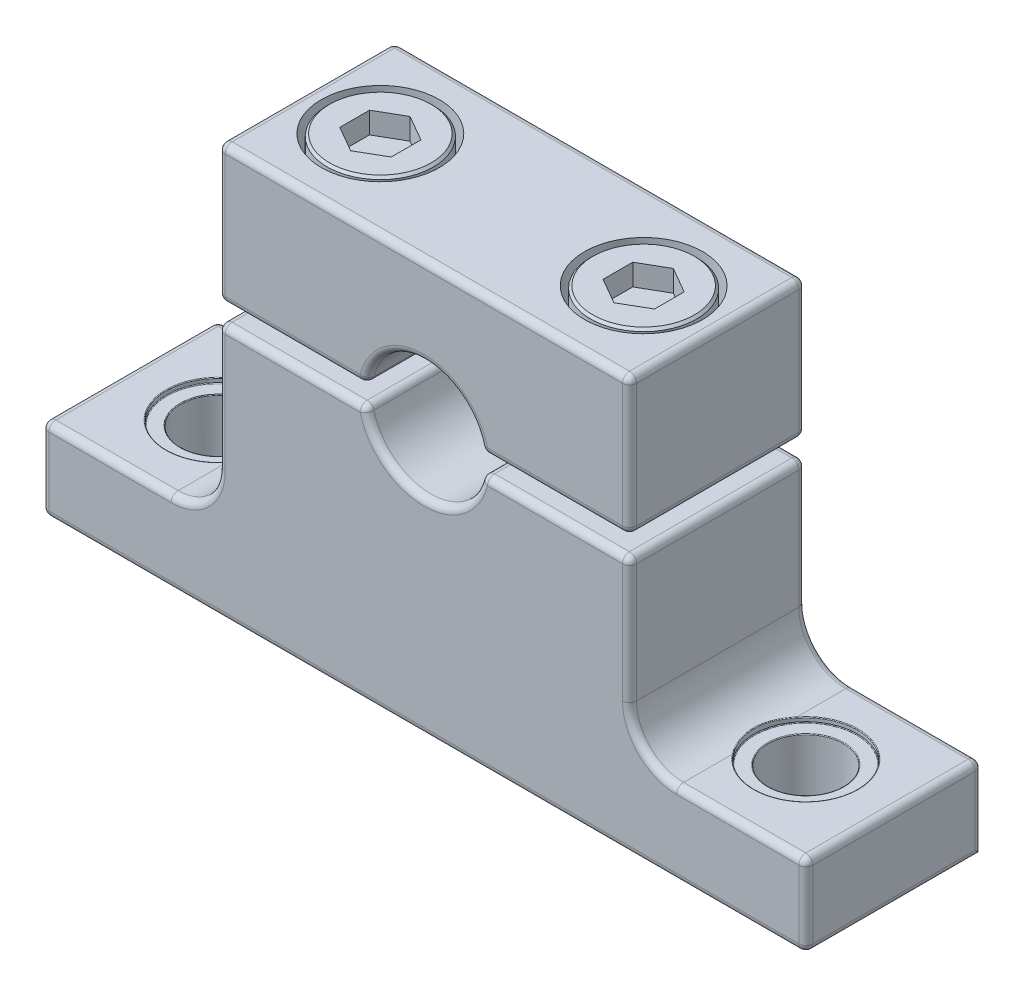
SolidWorks part; units mm, degrees
ref_plane "Front" through (0, 0, 0) normal (0, 0, 1) x (1, 0, 0)
ref_plane "Top" through (0, 0, 0) normal (0, 1, 0) x (1, 0, 0)
ref_plane "Right" through (0, 0, 0) normal (1, 0, 0) x (0, 0, -1)
sketch "Sketch1" plane through (0, 0, 0) normal (0, 0, 1) x (1, 0, 0)
  line L0 (0, 22.225) -> (0, 0) construction
  line L1 (-20.6375, 0) -> (20.6375, 0) construction
  line L2 (0, 0) -> (0, 14.2875) construction
  line L3 (-15.875, 0) -> (15.875, 0) construction
  line L4 (13.843, 0) -> (17.907, 0) construction
  line L5 (17.907, 0) -> (17.907, 1.27) construction
  line L6 (13.843, 0) -> (13.843, 1.27) construction
  line L7 (-13.843, 0) -> (-13.843, 1.27) construction
  line L8 (-17.907, 0) -> (-17.907, 1.27) construction
  line L9 (-13.843, 0) -> (-17.907, 0) construction
  line L10 (-11.1125, 14.2875) -> (11.1125, 14.2875) construction
  line L11 (-11.1125, 13.7795) -> (11.1125, 13.7795) construction
  line L12 (-11.1125, 14.7955) -> (11.1125, 14.7955) construction
  line L13 (13.462, 0) -> (13.462, 1.27) construction
  line L14 (18.288, 0) -> (18.288, 1.27) construction
  line L15 (-13.462, 0) -> (-13.462, 1.27) construction
  line L16 (-18.288, 0) -> (-18.288, 1.27) construction
  line L17 (-11.0713, 13.7795) -> (11.0713, 13.7795) construction
  line L18 (-11.0713, 14.7955) -> (11.0713, 14.7955) construction
  line L19 (-11.0713, 14.2875) -> (11.0713, 14.2875) construction
  line L20 (-20.6375, 0) -> (-20.6375, 4.445) construction
  line L21 (-20.6375, 4.445) -> (-11.1125, 4.445) construction
  line L22 (-11.1125, 13.7795) -> (-11.1125, 4.445) construction
  line L23 (-11.1125, 14.7955) -> (-11.1125, 22.225) construction
  line L24 (-11.1125, 22.225) -> (11.1125, 22.225) construction
  line L25 (20.6375, 0) -> (20.6375, 4.445) construction
  line L26 (20.6375, 4.445) -> (11.1125, 4.445) construction
  line L27 (11.1125, 13.7795) -> (11.1125, 4.445) construction
  line L28 (11.1125, 14.7955) -> (11.1125, 22.225) construction
  line L29 (0, 22.225) -> (0, 18.7198) construction
  line L30 (0.3175, 18.7198) -> (-0.3175, 18.7198) construction
  line L31 (11.1125, 4.445) -> (11.1125, 0) construction
  line L32 (-15.875, 0) -> (-15.875, 4.445) construction
  line L33 (0, 17.4625) -> (11.1125, 17.4625) construction
  line L34 (0, 11.1125) -> (11.1125, 11.1125) construction
  circle A0 centre (0, 14.2875) radius 3.175 construction
  arc A1 (-13.6525, 4.445) -> (-11.1125, 6.985) centre (-13.6525, 6.985) ccw construction
  arc A2 (13.6525, 4.445) -> (11.1125, 6.985) centre (13.6525, 6.985) cw construction
  point P5 (0, 0)
  point P9 (0, 14.2875)
  point P11 (0, 0)
  point P12 (15.875, 0)
  point P13 (-15.875, 0)
  point P16 (15.875, 0)
  point P37 (0, 13.7795)
  point P40 (0, 14.7955)
  point P60 (0, 18.7198)
  point P64 (15.875, 4.445)
  dimension "D1" = 1.27
  dimension "D8" = 4.445
  dimension "D12" = 0.635
  dimension "Radius" = 2.54
  dimension "D9" = 4.7625
  dimension "D3" = 0.508
  dimension "D4" = 0.381
  dimension "D5" = 0.381
  dimension "D6" = 0.381
  dimension "D7" = 0.381
sketch "Sketch3" plane through (0, 0, 0) normal (0, 0, 1) x (1, 0, 0)
  line L0 (-11.1125, 22.225) -> (11.1125, 22.225) construction
  line L1 (11.1125, 14.7955) -> (11.1125, 22.225) construction
  line L2 (-11.1125, 14.7955) -> (11.1125, 14.7955) construction
  line L3 (-11.1125, 14.7955) -> (-11.1125, 22.225) construction
  line L4 (-11.1125, 13.7795) -> (-11.1125, 4.445) construction
  line L5 (-20.6375, 4.445) -> (-11.1125, 4.445) construction
  line L6 (-20.6375, 0) -> (-20.6375, 4.445) construction
  line L7 (-20.6375, 0) -> (20.6375, 0) construction
  line L8 (20.6375, 0) -> (20.6375, 4.445) construction
  line L9 (20.6375, 4.445) -> (11.1125, 4.445) construction
  line L10 (11.1125, 13.7795) -> (11.1125, 4.445) construction
  line L11 (-11.1125, 13.7795) -> (11.1125, 13.7795) construction
  line L12 (-11.1125, 22.225) -> (11.1125, 22.225)
  line L13 (11.1125, 14.7955) -> (11.1125, 22.225)
  line L14 (-11.1125, 14.7955) -> (-3.1341, 14.7955)
  line L15 (-11.1125, 14.7955) -> (-11.1125, 22.225)
  line L16 (-11.1125, 13.7795) -> (-11.1125, 6.985)
  line L17 (-20.6375, 4.445) -> (-13.6525, 4.445)
  line L18 (-20.6375, 0) -> (-20.6375, 4.445)
  line L19 (-20.6375, 0) -> (20.6375, 0)
  line L20 (20.6375, 0) -> (20.6375, 4.445)
  line L21 (20.6375, 4.445) -> (13.6525, 4.445)
  line L22 (11.1125, 13.7795) -> (11.1125, 6.985)
  line L23 (-11.1125, 13.7795) -> (-3.1341, 13.7795)
  line L24 (3.1341, 14.7955) -> (11.1125, 14.7955)
  line L25 (3.1341, 13.7795) -> (11.1125, 13.7795)
  arc A0 (-13.6525, 4.445) -> (-11.1125, 6.985) centre (-13.6525, 6.985) ccw construction
  arc A1 (11.1125, 6.985) -> (13.6525, 4.445) centre (13.6525, 6.985) ccw construction
  circle A2 centre (0, 14.2875) radius 3.175 construction
  arc A3 (-13.6525, 4.445) -> (-11.1125, 6.985) centre (-13.6525, 6.985) ccw
  arc A4 (11.1125, 6.985) -> (13.6525, 4.445) centre (13.6525, 6.985) ccw
  arc A5 (3.1341, 14.7955) -> (-3.1341, 14.7955) centre (0, 14.2875) ccw
  arc A6 (-3.1341, 13.7795) -> (3.1341, 13.7795) centre (0, 14.2875) ccw
extrude "Boss-Extrude1" add sketch "Sketch3" against normal blind 9.525
sketch "Sketch4" plane through (0, 0, 0) normal (0, -1, 0) x (1, 0, 0)
  line L0 (-20.6375, 0) -> (-20.6375, -9.525) construction
  line L1 (-20.6375, 0) -> (-11.1125, 0) construction
  line L2 (-20.6375, -4.7625) -> (20.6375, -4.7625) construction
  line L3 (20.6375, -9.525) -> (20.6375, 0) construction
  line L4 (-15.875, 0) -> (-15.875, -9.525) construction
  line L5 (15.875, 0) -> (15.875, -9.525) construction
  line L6 (-20.6375, -9.525) -> (20.6375, -9.525) construction
  line L7 (0, 0) -> (0, -9.525) construction
  circle A0 centre (-15.875, -4.7625) radius 2.032
  circle A1 centre (15.875, -4.7625) radius 2.032
  point P7 (-20.6375, -4.7625)
  dimension "D1" = 4.064
extrude "Cut-Extrude1" cut sketch "Sketch4" against normal through all
sketch "Sketch6" plane through (0, 4.445, 0) normal (0, 1, 0) x (1, 0, 0)
  line L0 (0, 0) -> (0, 9.525) construction
  line L1 (-20.6375, 0) -> (20.6375, 0) construction
  line L2 (11.1125, 9.525) -> (-11.1125, 9.525) construction
  circle A1 centre (-15.875, 4.7625) radius 2.032 construction
  circle A2 centre (-15.875, 4.7625) radius 2.032
  circle A4 centre (-15.875, 4.7625) radius 2.413
  circle A5 centre (15.875, 4.7625) radius 2.413
  dimension "D1" = 0.381
sketch "Sketch7" plane through (0, 0, 0) normal (0, 0, 1) x (1, 0, 0)
  line L0 (-20.6375, 4.191) -> (20.6375, 4.191) construction
  line L1 (-11.1125, 13.7795) -> (-11.1125, 0) construction
  line L2 (-20.6375, 0) -> (20.6375, 0) construction
  line L3 (11.1125, 13.7795) -> (11.1125, 0) construction
  line L5 (-20.6375, 0) -> (-20.6375, 4.445) construction
  line L6 (-20.6375, 4.445) -> (-11.1125, 4.445) construction
  line L7 (20.6375, 0) -> (20.6375, 4.445) construction
  line L8 (-15.875, 4.445) -> (-15.875, 4.191) construction
  line L9 (15.875, 4.445) -> (15.875, 4.191) construction
  line L10 (20.6375, 4.445) -> (11.1125, 4.445) construction
  dimension "D1" = 0.254
sketch "Sketch8" plane through (0, 13.7795, 0) normal (0, 1, 0) x (1, 0, 0)
  line L0 (0, 0) -> (0, 9.525) construction
  line L1 (11.1125, 9.525) -> (-11.1125, 9.525) construction
  circle A0 centre (-15.875, 4.7625) radius 2.413 construction
  circle A1 centre (15.875, 4.7625) radius 2.413 construction
  circle A2 centre (-15.875, 4.7625) radius 2.413 construction
  circle A3 centre (15.875, 4.7625) radius 2.413 construction
  circle A4 centre (-15.875, 4.7625) radius 2.794
  circle A5 centre (15.875, 4.7625) radius 2.794
  dimension "CounterBoreID" = 5.588
extrude "Cut-Extrude3" cut sketch "Sketch8" against normal up to vertex (9.5885 mm away) up to point (-15.875, 4.191, 0)
sketch "Sketch10" plane through (0, 22.225, 0) normal (0, 1, 0) x (1, 0, 0)
  line L0 (-11.1125, 9.525) -> (-11.1125, 0) construction
  line L1 (11.1125, 9.525) -> (11.1125, 0) construction
  line L2 (-11.1125, 9.525) -> (-11.1125, 0) construction
  line L3 (11.1125, 9.525) -> (11.1125, 0) construction
  line L4 (-9.9822, 9.525) -> (-9.9822, 0) construction
  line L5 (0, 0) -> (0, 9.525) construction
  line L6 (9.9822, 9.525) -> (9.9822, 0) construction
  circle A0 centre (-7.112, 4.7625) radius 1.7526 construction
  circle A1 centre (7.112, 4.7625) radius 2.0066
  circle A2 centre (-7.112, 4.7625) radius 2.0066
  circle A3 centre (7.112, 4.7625) radius 1.7526 construction
  circle A4 centre (-7.112, 4.7625) radius 2.8702 construction
  circle A5 centre (7.112, 4.7625) radius 2.8702 construction
extrude "Cut-Extrude4" cut sketch "Sketch10" against normal through all
ref_plane "Plane1" through (0, 0, -4.7625) normal (0, 0, 1) x (1, 0, 0)
sketch "Sketch12" plane through (0, 22.225, 0) normal (0, 1, 0) x (1, 0, 0)
  line L0 (0, 9.525) -> (0, 0) construction
  circle A0 centre (-7.112, 4.7625) radius 3.0607 construction
  circle A1 centre (7.112, 4.7625) radius 3.1877
  circle A2 centre (-7.112, 4.7625) radius 3.1877
  circle A3 centre (7.112, 4.7625) radius 3.0607 construction
  dimension "D2" = 6.3754
  dimension "D1" = 0.127
extrude "Cut-Extrude5" cut sketch "Sketch12" against normal blind 3.8862
sketch "Sketch13" plane through (0, 0, 0) normal (0, 1, 0) x (1, 0, 0)
  line L0 (-7.112, 9.525) -> (-7.112, 0) construction
  line L1 (11.1125, 9.525) -> (-11.1125, 9.525) construction
  line L2 (0, 9.525) -> (0, 0) construction
  line L3 (7.112, 9.525) -> (7.112, 0) construction
  circle A0 centre (-7.112, 4.7625) radius 2.0066 construction
  point P2 (-7.112, 4.7625)
  point P9 (-7.112, 9.525)
  point P10 (-7.112, 0)
  point P17 (7.112, 9.525)
  point P18 (7.112, 0)
  dimension "D1" = 4.0132
sketch "Sketch15" plane through (0, 0, -4.7625) normal (0, 0, 1) x (1, 0, 0)
  line L0 (-7.112, 8.89) -> (-7.112, 22.225) construction
  line L1 (-7.112, 22.225) -> (-9.9822, 22.225) construction
  line L2 (-9.9822, 22.225) -> (-9.9822, 18.7198) construction
  line L3 (-9.9822, 18.7198) -> (-8.8646, 18.7198) construction
  line L4 (-8.8646, 18.7198) -> (-8.8646, 8.89) construction
  line L5 (-8.8646, 8.89) -> (-7.112, 8.89) construction
  line L8 (-11.1125, 22.225) -> (11.1125, 22.225) construction
  line L9 (-7.112, 8.89) -> (-7.112, 22.225)
  line L10 (-7.112, 22.225) -> (-9.9822, 22.225)
  line L11 (-9.9822, 22.225) -> (-9.9822, 18.7198)
  line L12 (-9.9822, 18.7198) -> (-8.8646, 18.7198)
  line L13 (-8.8646, 18.7198) -> (-8.8646, 8.89)
  line L14 (-8.8646, 8.89) -> (-7.112, 8.89)
  dimension "D2" = 2.8702
  dimension "D1" = 3.5052
  dimension "D3" = 1.7526
  dimension "Screw Length" = 13.335
revolve "Revolve1" add sketch "Sketch15" angle 360 about L9
chamfer "Chamfer1" distance 0.127 angle 45 1 edges at (-7.112, 22.225, -7.6327)
sketch "Sketch16" plane through (0, 22.225, 0) normal (0, 1, 0) x (1, 0, 0)
  line L0 (-7.112, 9.525) -> (-7.112, 0) construction
  line L1 (-7.112, 6.3665) -> (-8.5011, 5.5645)
  line L2 (-8.5011, 5.5645) -> (-8.5011, 3.9605)
  line L3 (-8.5011, 3.9605) -> (-7.112, 3.1585)
  line L4 (-7.112, 3.1585) -> (-5.7229, 3.9605)
  line L5 (-5.7229, 3.9605) -> (-5.7229, 5.5645)
  line L6 (-5.7229, 5.5645) -> (-7.112, 6.3665)
  circle A0 centre (-7.112, 4.7625) radius 1.3891 construction
  dimension "Hex Size" = 2.7781
extrude "Cut-Extrude6" cut sketch "Sketch16" against normal blind 1.1567
mirror "Mirror1" about plane through (0, 0, 0) normal (1, 0, 0) of bodies 121 119
fillet "Fillet1" radius 0.381 18 edges at (0, 22.225, -9.525) (-11.1125, 22.225, -4.7625) (-11.1125, 18.5103, -9.525) (-11.1125, 18.5103, 0) (11.1125, 18.5103, -9.525) (11.1125, 22.225, -4.7625) (11.1125, 18.5103, 0) (0, 22.225, 0) (11.1125, 14.7955, -4.7625) (7.1233, 14.7955, -9.525) (-7.1233, 14.7955, -9.525) (-11.1125, 14.7955, -4.7625) (-7.1233, 14.7955, 0) (7.1233, 14.7955, 0) (0, 17.4625, -9.525) (0, 17.4625, 0) (3.1341, 14.7955, -4.7625) (-3.1341, 14.7955, -4.7625)
fillet "Fillet2" radius 0.381 31 edges at (17.145, 4.445, -9.525) (11.8564, 5.1889, -9.525) (11.1125, 10.3822, 0) (11.8564, 5.1889, 0) (-17.145, 4.445, 0) (-11.8564, 5.1889, 0) (-17.145, 4.445, -9.525) (-11.8564, 5.1889, -9.525) (11.1125, 10.3822, -9.525) (20.6375, 0, -4.7625) (20.6375, 2.2225, -9.525) (20.6375, 4.445, -4.7625) (17.145, 4.445, 0) (20.6375, 2.2225, 0) (0, 0, 0) (-20.6375, 2.2225, -9.525) (-20.6375, 0, -4.7625) (-20.6375, 4.445, -4.7625) (-20.6375, 2.2225, 0) (-11.1125, 10.3822, 0) (-11.1125, 10.3822, -9.525) (11.1125, 13.7795, -4.7625) (-11.1125, 13.7795, -4.7625) (-7.1233, 13.7795, 0) (7.1233, 13.7795, 0) (7.1233, 13.7795, -9.525) (-7.1233, 13.7795, -9.525) (0, 11.1125, -9.525) (0, 11.1125, 0) (3.1341, 13.7795, -4.7625) (-3.1341, 13.7795, -4.7625)
fillet "Fillet3" radius 0.0381 8 edges at (-18.669, 4.191, -4.7625) (18.669, 4.191, -4.7625) (18.669, 4.445, -4.7625) (13.1365, 4.498, -5.3167) (17.907, 4.191, -4.7625) (-13.0815, 4.51, -4.8151) (-18.669, 4.445, -4.7625) (-17.907, 4.191, -4.7625)
ref_plane "Contact Plane 1" through (0, 0, -4.7625) normal (0, 0, -1) x (-1, 0, 0)
ref_plane "Contact Plane 2" through (0, 0, 0) normal (-1, 0, 0) x (0, 0, 1)
ref_plane "Contact Plane 3" through (0, 11.1125, 0) normal (0, 1, 0) x (1, 0, 0)
ref_plane "Contact Plane 4" through (0, 22.225, 0) normal (0, 1, 0) x (1, 0, 0)
ref_plane "Contact Plane 5" through (0, 0, 0) normal (0, -1, 0) x (-1, 0, 0)
ref_plane "Contact Plane 6" through (20.6375, 0, 0) normal (1, 0, 0) x (0, 0, -1)
ref_plane "Contact Plane 7" through (-20.6375, 0, 0) normal (-1, 0, 0) x (0, 0, 1)
ref_axis "Center Axis 1" through (0, 54.8037, -4.7625) along (0, -1, 0)
ref_axis "Center Axis 2" through (0, 11.1125, -33.3184) along (0, 0, 1)
ref_axis "Center Axis 3" through (69.4309, 11.1125, -4.7625) along (-1, 0, 0)
equation "\"D8@Sketch1\"=\"Oall Ht@Sketch1\"*.20"
equation "\"D1@Sketch4\"= \"HoldDia@Sketch1\""
equation "\"D1@Cut-Extrude5\"=\"HeadDp@Sketch1\"+.015"
equation "\"D1@Sketch15\"=\"HeadDp@Sketch1\""
equation "\"D3@Sketch15\"=\"ThrdDia@Sketch10\"*.5"
equation "\"D1@Cut-Extrude6\"= \"HeadDp@Sketch1\"*.33"
equation "\"D2@Sketch12\"=\"Head Dia@Sketch10\"+.025"
equation "\"D2@Sketch15\"=\"Head Dia@Sketch10\"*.50"
